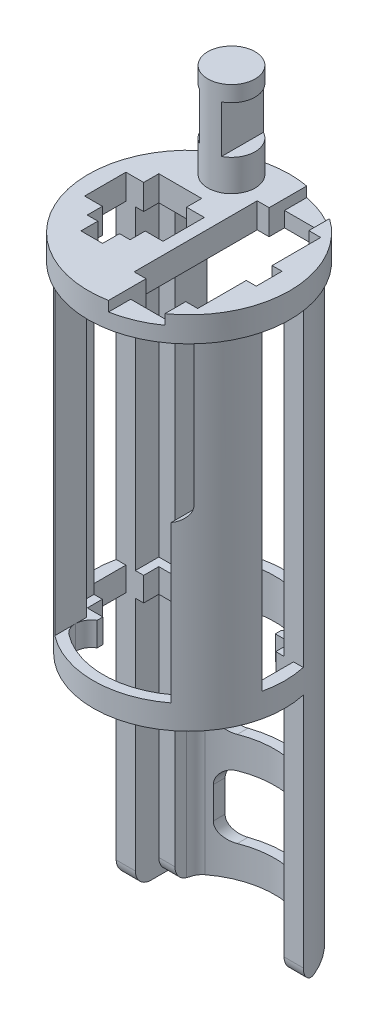
SolidWorks part; units mm, degrees
material "FormLabs Tough SLA- 3-D Printed"
ref_plane "Front Plane" through (0, 0, 0) normal (0, 0, 1) x (1, 0, 0)
ref_plane "Top Plane" through (0, 0, 0) normal (0, 1, 0) x (1, 0, 0)
ref_plane "Right Plane" through (0, 0, 0) normal (1, 0, 0) x (0, 0, -1)
sketch "Sketch2" plane through (0, 0, 0) normal (0, 1, 0) x (1, 0, 0)
  line L0 (23.0638, -3.692) -> (21.5138, -3.692) construction
  line L1 (23.0638, -2.492) -> (27.9638, -2.492) construction
  line L2 (23.0638, -2.492) -> (23.0638, -3.692) construction
  line L3 (23.0638, -8.892) -> (35.4638, -8.892) construction
  line L4 (35.4638, -2.492) -> (35.4638, -3.692) construction
  line L5 (21.5138, -3.692) -> (21.5138, -7.692) construction
  line L6 (21.5138, -7.692) -> (23.0638, -7.692) construction
  line L7 (35.4638, -3.692) -> (37.0138, -3.692) construction
  line L8 (37.0138, -3.692) -> (37.0138, -7.692) construction
  line L9 (37.0138, -7.692) -> (35.4638, -7.692) construction
  line L10 (27.9638, -2.492) -> (27.9638, -1.492) construction
  line L11 (27.9638, -1.492) -> (30.5638, -1.492) construction
  line L12 (30.5638, -1.492) -> (30.5638, -2.492) construction
  line L13 (21.5138, -5.692) -> (23.0638, -5.692) construction
  line L14 (23.0638, -5.692) -> (35.4638, -5.692) construction
  line L15 (35.4638, -5.692) -> (37.0138, -5.692) construction
  line L16 (23.0638, -7.692) -> (23.0638, -8.892) construction
  line L17 (35.4638, -7.692) -> (35.4638, -8.892) construction
  line L18 (23.0638, -3.692) -> (23.0638, -5.692) construction
  line L19 (23.0638, -5.692) -> (23.0638, -7.692) construction
  line L20 (35.4638, -7.692) -> (35.4638, -5.692) construction
  line L21 (35.4638, -5.692) -> (35.4638, -3.692) construction
  line L22 (29.2638, -5.692) -> (29.2638, -1.492) construction
  line L23 (30.5638, -2.492) -> (35.4638, -2.492) construction
  line L24 (6.6548, -2.0828) -> (8.4455, -2.0828)
  line L29 (6.6548, -3.6068) -> (1.0922, -3.6068) construction
  line L30 (6.6548, -3.6068) -> (6.6548, -2.0828)
  line L31 (6.6548, 3.6068) -> (-6.6548, 3.6068) construction
  line L32 (-6.6548, -3.6068) -> (-6.6548, -2.0828)
  line L33 (8.4455, -2.0828) -> (8.4455, 2.0828)
  line L34 (8.4455, 2.0828) -> (6.6548, 2.0828)
  line L35 (-6.6548, -2.0828) -> (-8.4455, -2.0828)
  line L36 (-8.4455, -2.0828) -> (-8.4455, 2.0828)
  line L37 (-8.4455, 2.0828) -> (-6.6548, 2.0828)
  line L38 (1.0922, -3.6068) -> (1.0922, -5.3086) construction
  line L39 (1.0922, -5.3086) -> (-1.0922, -5.3086) construction
  line L40 (-1.0922, -5.3086) -> (-1.0922, -3.6068) construction
  line L41 (8.4455, 0) -> (6.6548, 0) construction
  line L42 (6.6548, 0) -> (-6.6548, 0) construction
  line L43 (-6.6548, 0) -> (-8.4455, 0) construction
  line L44 (6.6548, 2.0828) -> (6.6548, 3.6068)
  line L45 (-6.6548, 2.0828) -> (-6.6548, 3.6068)
  line L46 (6.6548, -2.0828) -> (6.6548, 0) construction
  line L47 (6.6548, 0) -> (6.6548, 2.0828) construction
  line L48 (-6.6548, 2.0828) -> (-6.6548, 0) construction
  line L49 (-6.6548, 0) -> (-6.6548, -2.0828) construction
  line L50 (-6.6548, 3.6068) -> (-5.08, 3.6068)
  line L51 (-1.0922, -3.6068) -> (-6.6548, -3.6068) construction
  line L52 (-5.08, 3.6068) -> (-5.08, 4.191)
  line L53 (-8.1351, 5.1943) -> (8.1351, 5.1943) construction
  line L54 (-1.9685, -3.6068) -> (-1.9685, -6.6548) construction
  line L55 (-1.9685, -6.6548) -> (1.9685, -6.6548) construction
  line L56 (1.9685, -6.6548) -> (1.9685, -3.6068) construction
  line L57 (0, -6.6548) -> (0, -5.3086) construction
  line L58 (37.0138, -3.692) -> (37.7638, -3.692) construction
  line L59 (37.7638, -3.692) -> (37.7638, -7.692) construction
  line L60 (37.7638, -7.692) -> (37.0138, -7.692) construction
  line L61 (21.5138, -3.692) -> (20.7638, -3.692) construction
  line L62 (20.7638, -3.692) -> (20.7638, -7.692) construction
  line L63 (20.7638, -7.692) -> (21.5138, -7.692) construction
  line L64 (8.4455, 2.0828) -> (9.525, 2.0828) construction
  line L65 (9.525, 2.0828) -> (9.525, -2.0828) construction
  line L66 (9.525, -2.0828) -> (8.4455, -2.0828) construction
  line L67 (-8.4455, -2.0828) -> (-9.525, -2.0828) construction
  line L68 (-9.525, -2.0828) -> (-9.525, 2.0828) construction
  line L69 (-9.525, 2.0828) -> (-8.4455, 2.0828) construction
  line L73 (6.6548, 3.6068) -> (5.08, 3.6068)
  line L75 (0, 5.1943) -> (0, 9.652) construction
  line L76 (5.08, 3.6068) -> (5.08, 4.191)
  line L77 (6.6548, -3.6068) -> (5.08, -3.6068)
  line L78 (5.08, -3.6068) -> (5.08, -4.191)
  line L79 (-6.6548, -3.6068) -> (-5.08, -3.6068)
  line L80 (-5.08, -3.6068) -> (-5.08, -4.191)
  line L81 (-6.6548, 3.6068) -> (-6.6548, 4.191) construction
  line L82 (-6.6548, 4.191) -> (-5.08, 4.191) construction
  line L83 (6.6548, 3.6068) -> (6.6548, 4.191) construction
  line L84 (6.6548, 4.191) -> (5.08, 4.191) construction
  line L85 (-6.6548, -3.6068) -> (-6.6548, -4.191) construction
  line L86 (-6.6548, -4.191) -> (-5.08, -4.191) construction
  line L87 (6.6548, -3.6068) -> (6.6548, -4.191) construction
  line L88 (6.6548, -4.191) -> (5.08, -4.191) construction
  line L89 (5.08, -4.191) -> (5.8674, -4.191)
  line L90 (5.8674, -4.191) -> (5.8674, -6.3367)
  line L91 (-5.08, -4.191) -> (-5.8674, -4.191)
  line L92 (-5.8674, -4.191) -> (-5.8674, -6.3367)
  line L93 (-5.08, 4.191) -> (-5.8674, 4.191)
  line L94 (-5.8674, 4.191) -> (-5.8674, 6.3367)
  line L95 (5.08, 4.191) -> (5.8674, 4.191)
  line L96 (5.8674, 4.191) -> (5.8674, 6.3367)
  line L97 (6.6548, 4.191) -> (7.239, 4.191) construction
  line L98 (7.239, 4.191) -> (7.239, 2.0828) construction
  line L99 (6.6548, -4.191) -> (7.239, -4.191) construction
  line L100 (7.239, -4.191) -> (7.239, -2.0828) construction
  line L101 (-6.6548, -4.191) -> (-7.239, -4.191) construction
  line L102 (-7.239, -4.191) -> (-7.239, -2.0828) construction
  line L103 (-6.6548, 4.191) -> (-7.239, 4.191) construction
  line L104 (-7.239, 4.191) -> (-7.239, 2.0828) construction
  circle A1 centre (0, 0) radius 9.652
  arc A4 (-5.8674, -6.3367) -> (5.8674, -6.3367) centre (0, 0) ccw
  arc A5 (5.8674, 6.3367) -> (-5.8674, 6.3367) centre (0, 0) ccw
  point P85 (-5.8674, 4.191)
  point P86 (-5.08, 3.8989)
  dimension "D2" = 4
  dimension "D15" = 19.304
  dimension "D16" = 1.016
  dimension "D21" = 10.16
  dimension "D22" = 8.382
  dimension "D3" = 6.4
  dimension "D4" = 7.4
  dimension "D5" = 2.6
  dimension "D6" = 12.4
  dimension "D7" = 15.5
  dimension "D8" = 4.1656
  dimension "D9" = 7.2136
  dimension "D10" = 8.9154
  dimension "D11" = 2.1844
  dimension "D12" = 13.3096
  dimension "D13" = 16.891
  dimension "D14" = 1.5875
  dimension "D17" = 3.048
  dimension "D18" = 3.937
  dimension "D19" = 17
  dimension "D20" = 19.05
extrude "Boss-Extrude1" add sketch "Sketch2" along normal blind 2.413
sketch "Sketch3" plane through (0, 2.413, 0) normal (0, 1, 0) x (1, 0, 0)
  line L5 (6.6548, 0) -> (-6.6548, 0) construction
  line L6 (-5.8674, 7.6639) -> (-5.8674, 4.445)
  line L7 (-5.8674, 4.191) -> (-5.8674, 6.3367) construction
  line L8 (-5.8674, 4.445) -> (-7.493, 4.445)
  line L9 (-7.493, 4.445) -> (-7.493, 2.0828)
  line L10 (-8.4455, 2.0828) -> (-6.6548, 2.0828) construction
  line L11 (-7.493, 2.0828) -> (-9.4246, 2.0828)
  line L12 (-9.525, 2.0828) -> (-8.4455, 2.0828) construction
  line L13 (-5.8674, -7.6639) -> (-5.8674, -4.445)
  line L14 (-5.8674, -4.191) -> (-5.8674, -6.3367) construction
  line L15 (-5.8674, -4.445) -> (-7.493, -4.445)
  line L16 (-7.493, -4.445) -> (-7.493, -2.0828)
  line L17 (-6.6548, -2.0828) -> (-8.4455, -2.0828) construction
  line L18 (-7.493, -2.0828) -> (-9.4246, -2.0828)
  line L19 (-8.4455, -2.0828) -> (-9.525, -2.0828) construction
  line L20 (5.8674, -7.6639) -> (5.8674, -4.445)
  line L21 (5.8674, -4.191) -> (5.8674, -6.3367) construction
  line L22 (5.8674, -4.445) -> (7.493, -4.445)
  line L23 (7.493, -4.445) -> (7.493, -2.0828)
  line L24 (6.6548, -2.0828) -> (8.4455, -2.0828) construction
  line L25 (7.493, -2.0828) -> (9.4246, -2.0828)
  line L26 (9.525, -2.0828) -> (8.4455, -2.0828) construction
  line L27 (5.8674, 7.6639) -> (5.8674, 4.445)
  line L28 (5.8674, 4.191) -> (5.8674, 6.3367) construction
  line L29 (5.8674, 4.445) -> (7.493, 4.445)
  line L30 (7.493, 4.445) -> (7.493, 2.0828)
  line L31 (8.4455, 2.0828) -> (6.6548, 2.0828) construction
  line L32 (7.493, 2.0828) -> (9.4246, 2.0828)
  line L33 (8.4455, 2.0828) -> (9.525, 2.0828) construction
  line L34 (7.239, 4.191) -> (7.239, 2.0828) construction
  line L35 (6.6548, 4.191) -> (5.08, 4.191) construction
  arc A5 (5.8674, -7.6639) -> (9.4246, -2.0828) centre (0, 0) ccw
  circle A6 centre (0, 0) radius 9.652 construction
  arc A7 (-5.8674, 7.6639) -> (-9.4246, 2.0828) centre (0, 0) ccw
  arc A8 (-9.4246, -2.0828) -> (-5.8674, -7.6639) centre (0, 0) ccw
  arc A9 (9.4246, 2.0828) -> (5.8674, 7.6639) centre (0, 0) ccw
  dimension "D1" = 0.254
  dimension "D2" = 0.254
extrude "Boss-Extrude2" add sketch "Sketch3" along normal blind 31.75
sketch "Sketch4" plane through (0, 34.163, 0) normal (0, 1, 0) x (1, 0, 0)
  line L0 (0.6674, -6.2) -> (0.6674, 6.2)
  line L1 (0.6674, 6.2) -> (1.8674, 6.2)
  line L2 (7.0674, 6.2) -> (7.0674, 1.3)
  line L3 (7.0674, 1.3) -> (8.0674, 1.3)
  line L4 (8.0674, 1.3) -> (8.0674, -1.3)
  line L5 (8.0674, -1.3) -> (7.0674, -1.3)
  line L6 (7.0674, -1.3) -> (7.0674, -6.2)
  line L7 (7.0674, -6.2) -> (5.8674, -6.2)
  line L8 (5.8674, -6.2) -> (5.8674, -7.75)
  line L9 (5.8674, -7.75) -> (1.8674, -7.75)
  line L10 (1.8674, -7.75) -> (1.8674, -6.2)
  line L11 (1.8674, -6.2) -> (0.6674, -6.2)
  line L12 (1.8674, 6.2) -> (1.8674, 7.75)
  line L13 (1.8674, 7.75) -> (5.8674, 7.75)
  line L14 (5.8674, 7.75) -> (5.8674, 6.2)
  line L15 (5.8674, 6.2) -> (7.0674, 6.2)
  line L16 (5.8674, -4.191) -> (5.8674, -6.3367) construction
  line L17 (35.4638, -3.692) -> (37.0138, -3.692) construction
  line L18 (23.0638, -2.492) -> (23.0638, -3.692) construction
  line L19 (30.5638, -1.492) -> (30.5638, -2.492) construction
  line L20 (21.5138, -3.692) -> (21.5138, -7.692) construction
  line L21 (5.8674, -7.75) -> (5.8674, -8.5) construction
  line L22 (23.0638, -8.892) -> (35.4638, -8.892) construction
  line L23 (30.5638, -2.492) -> (35.4638, -2.492) construction
  line L24 (-8.4455, 2.0828) -> (-6.6548, 2.0828) construction
  line L25 (5.8674, -8.5) -> (1.8674, -8.5) construction
  line L26 (1.8674, -8.5) -> (1.8674, -7.75) construction
  line L27 (5.8674, 7.75) -> (5.8674, 8.5) construction
  line L28 (5.8674, 8.5) -> (1.8674, 8.5) construction
  line L29 (1.8674, 8.5) -> (1.8674, 7.75) construction
  line L30 (-6.6548, -2.0828) -> (-8.4455, -2.0828) construction
  line L31 (21.5138, -3.692) -> (20.7638, -3.692) construction
  line L32 (-8.4455, 2.0828) -> (-6.6548, 2.0828)
  line L33 (-6.6548, 2.0828) -> (-6.6548, 3.6068)
  line L34 (-6.6548, 3.6068) -> (-2.3368, 3.6068)
  line L36 (-2.3368, 3.6068) -> (-2.3368, 2.0828)
  line L37 (-2.3368, 2.0828) -> (-0.5461, 2.0828)
  line L39 (-2.3368, -3.6068) -> (-3.4036, -3.6068)
  line L40 (-3.4036, -3.6068) -> (-3.4036, -5.3086)
  line L41 (-3.4036, -5.3086) -> (-5.588, -5.3086)
  line L42 (-5.588, -5.3086) -> (-5.588, -3.6068)
  line L43 (-5.588, -3.6068) -> (-6.6548, -3.6068)
  line L44 (1.0922, -3.6068) -> (1.0922, -5.3086) construction
  line L45 (1.0922, -5.3086) -> (-1.0922, -5.3086) construction
  line L46 (-6.6548, -3.6068) -> (-6.6548, -2.0828)
  line L47 (-6.6548, -2.0828) -> (-8.4455, -2.0828)
  line L48 (-8.4455, -2.0828) -> (-8.4455, 2.0828)
  line L49 (-2.3368, -3.6068) -> (-2.3368, -2.0828)
  line L50 (-2.3368, -2.0828) -> (-0.5461, -2.0828)
  line L51 (-0.5461, -2.0828) -> (-0.5461, 2.0828)
  line L52 (-4.4958, 3.6068) -> (-4.4958, -5.3086) construction
  line L53 (-0.5461, 2.0828) -> (0.5334, 2.0828) construction
  line L54 (0.5334, 2.0828) -> (0.5334, -2.0828) construction
  line L55 (0.5334, -2.0828) -> (-0.5461, -2.0828) construction
  line L56 (-8.4455, -2.0828) -> (-9.525, -2.0828) construction
  line L58 (8.4455, 0) -> (6.6548, 0) construction
  circle A0 centre (0, 0) radius 10.16
  point P78 (8.0674, 0)
  dimension "D3" = 20.32
  dimension "D1" = 4.318
  dimension "D2" = 7.8994
extrude "Boss-Extrude3" add sketch "Sketch4" along normal blind 2.54
sketch "Sketch5" plane through (0, 34.163, 0) normal (0, 1, 0) x (1, 0, 0)
  line L9 (20.7638, -7.692) -> (23.0638, -7.692) construction
  line L11 (7.493, -4.445) -> (5.8674, -4.445) construction
  line L12 (5.8674, 4.445) -> (7.0674, 4.445)
  line L13 (5.8674, 4.445) -> (5.8674, 7.6639)
  line L15 (7.0674, 4.445) -> (7.0674, 6.5737)
  line L17 (7.0674, -6.5737) -> (7.0674, -4.445)
  line L18 (7.0674, -4.445) -> (5.8674, -4.445)
  line L19 (5.8674, -7.6639) -> (5.8674, -4.445)
  line L20 (7.0674, -4.445) -> (5.8674, -4.445) construction
  line L21 (7.0674, -6.2) -> (7.0674, -1.3) construction
  line L22 (6.6548, 0) -> (-6.6548, 0) construction
  arc A3 (5.8674, -7.6639) -> (7.0674, -6.5737) centre (0, 0) ccw
  circle A4 centre (0, 0) radius 9.652 construction
  arc A5 (7.0674, 6.5737) -> (5.8674, 7.6639) centre (0, 0) ccw
  point P1 (0, 0)
  point P2 (0, 0)
  point P7 (5.8676, 7.6637)
  point P18 (5.8674, 7.6967)
  point P22 (5.8674, 7.6409)
  point P23 (5.8677, 7.6636)
  point P25 (5.8674, -7.4989)
  point P33 (5.8674, -7.6581)
extrude "Cut-Extrude1" cut sketch "Sketch5" against normal blind 16.002
sketch "Sketch6" plane through (0, 36.703, 0) normal (0, 1, 0) x (1, 0, 0)
  line L0 (6.6548, 3.6068) -> (-6.6548, 3.6068) construction
  line L1 (0.6674, 6.2) -> (0.6674, -6.2) construction
  circle A0 centre (-2.9312, 7.2054) radius 2.3812
  circle A1 centre (0, 0) radius 10.16 construction
  circle A2 centre (-2.9312, 7.2054) radius 3.5986 construction
  dimension "D1" = 4.7625
extrude "Boss-Extrude4" add sketch "Sketch6" along normal blind 9.525
sketch "Sketch7" plane through (0, 0, 0) normal (0, 0, 1) x (1, 0, 0)
  line L0 (-0.5499, 36.703) -> (-0.5499, 46.228) construction
  line L1 (-5.3124, 44.6405) -> (-4.0424, 44.6405)
  line L2 (-5.3124, 44.6405) -> (-5.3124, 39.878)
  line L3 (-5.3124, 39.878) -> (-4.0424, 39.878)
  line L4 (-4.0424, 44.6405) -> (-4.0424, 39.878)
  line L5 (-0.5499, 44.6405) -> (-1.8199, 44.6405)
  line L6 (-0.5499, 44.6405) -> (-0.5499, 39.878)
  line L7 (-0.5499, 39.878) -> (-1.8199, 39.878)
  line L8 (-1.8199, 44.6405) -> (-1.8199, 39.878)
  line L9 (-0.5499, 46.228) -> (-5.3124, 46.228) construction
  line L10 (10.16, 36.703) -> (-10.16, 36.703) construction
  line L11 (-5.3124, 46.228) -> (-5.3124, 36.703) construction
  dimension "D1" = 1.5875
  dimension "D2" = 1.27
  dimension "D3" = 3.175
extrude "Cut-Extrude2" cut sketch "Sketch7" against normal blind 9.525
sketch "Sketch9" plane through (0, 0, 0) normal (0, -1, 0) x (1, 0, 0)
  line L0 (6.6548, 0) -> (-6.6548, 0) construction
  line L9 (-5.8674, -6.3367) -> (-5.8674, -4.445)
  line L10 (-5.8674, -4.445) -> (-7.493, -4.445)
  line L11 (-7.493, -4.445) -> (-7.493, -2.0828)
  line L12 (-7.493, -2.0828) -> (-9.4246, -2.0828)
  line L13 (5.8674, -6.3367) -> (5.8674, -4.445)
  line L14 (5.8674, -4.445) -> (7.493, -4.445)
  line L15 (7.493, -4.445) -> (7.493, -2.0828)
  line L16 (7.493, -2.0828) -> (9.4246, -2.0828)
  arc A2 (-9.4246, -2.0828) -> (9.4246, -2.0828) centre (0, 0) ccw
  circle A4 centre (0, 0) radius 9.652 construction
  arc A7 (-5.8674, -6.3367) -> (5.8674, -6.3367) centre (0, 0) ccw
  arc A8 (-5.8674, -6.3367) -> (5.8674, -6.3367) centre (0, 0) ccw construction
extrude "Boss-Extrude5" add sketch "Sketch9" along normal blind 25.4
sketch "Sketch10" plane through (0, 0, 0) normal (0, 0, -1) x (-1, 0, 0)
  line L0 (-5.8674, 0) -> (5.8674, 0) construction
  line L1 (-4.7625, -15.875) -> (4.7625, -15.875)
  line L2 (-4.7625, -15.875) -> (-4.7625, -22.225)
  line L3 (-4.7625, -22.225) -> (4.7625, -22.225)
  line L4 (4.7625, -15.875) -> (4.7625, -22.225)
  line L5 (-9.4246, -25.4) -> (9.4246, -25.4) construction
  line L6 (0, 0) -> (0, -1.5875) construction
  line L11 (-4.7625, -1.5875) -> (4.7625, -1.5875)
  line L12 (-4.7625, -1.5875) -> (-4.7625, -12.7)
  line L13 (-4.7625, -12.7) -> (4.7625, -12.7)
  line L14 (4.7625, -1.5875) -> (4.7625, -12.7)
  dimension "D1" = 1.5875
  dimension "D2" = 3.175
  dimension "D3" = 9.525
  dimension "D4" = 6.35
  dimension "D5" = 3.175
extrude "Cut-Extrude3" cut sketch "Sketch10" along normal blind 12.7
fillet "Fillet4" radius 1.5875 8 edges at (-4.7625, -22.225, -7.7997) (4.7625, -22.225, -7.7997) (4.7625, -15.875, -7.7997) (-4.7625, -15.875, -7.7997) (-4.7625, -1.5875, -7.7997) (4.7625, -1.5875, -7.7997) (4.7625, -12.7, -7.7997) (-4.7625, -12.7, -7.7997)
fillet "Fillet5" radius 1.5875 5 edges at (5.8674, -11.4935, -6.3367) (-5.8674, -11.4935, -6.3367) (5.8674, 1.2065, 6.3367) (-5.8674, 1.2065, 6.3367) (-5.8674, 1.2065, 4.191) tangent propagation no
fillet "Fillet6" radius 1.5875 2 edges at (7.0674, 18.161, -5.5093) (7.0674, 18.161, 5.5093)
fillet "Fillet7" radius 1.5875 4 edges at (-6.6802, -25.4, -4.445) (6.6802, -25.4, -4.445) (8.4588, -25.4, -2.0828) (-8.4588, -25.4, -2.0828)
sketch "Sketch11" plane through (0, 36.703, 0) normal (0, 1, 0) x (1, 0, 0)
  line L0 (1.8674, 7.75) -> (1.8674, 9.9869)
  line L1 (5.8674, 7.75) -> (5.8674, 8.2945)
  line L2 (5.8674, -7.75) -> (5.8674, -8.2945)
  line L3 (1.8674, -7.75) -> (1.8674, -9.9869)
  line L4 (1.8674, 7.75) -> (5.8674, 7.75)
  line L5 (1.8674, -7.75) -> (5.8674, -7.75)
  arc A0 (1.8674, -9.9869) -> (5.8674, -8.2945) centre (0, 0) ccw
  circle A1 centre (0, 0) radius 10.16 construction
  arc A2 (5.8674, 8.2945) -> (1.8674, 9.9869) centre (0, 0) ccw
extrude "Cut-Extrude4" cut sketch "Sketch11" against normal offset from surface (1.016 mm away) 1.524 up to face at (-5.585, 34.163, 0.6858)
sketch "Sketch12" plane through (0, 0, 0) normal (0, -1, 0) x (1, 0, 0)
  line L0 (5.8674, 4.191) -> (5.8674, 5.6003)
  line L1 (5.8674, 5.6003) -> (5.8674, 4.191) construction
  line L2 (5.8674, 4.191) -> (5.08, 4.191)
  line L3 (5.8674, -4.191) -> (5.8674, -5.6003)
  line L4 (5.8674, -4.445) -> (5.8674, -5.6003) construction
  line L5 (5.8674, -4.191) -> (5.08, -4.191)
  line L6 (-5.8674, -4.191) -> (-5.8674, -5.6003)
  line L7 (-5.8674, -4.445) -> (-5.8674, -7.6639) construction
  line L8 (-5.8674, -4.191) -> (-5.08, -4.191)
  arc A0 (5.08, -4.191) -> (5.8674, -5.6003) centre (4.2124, -5.6003) cw
  arc A1 (-5.8674, -5.6003) -> (-5.08, -4.191) centre (-4.2124, -5.6003) cw
  arc A2 (5.8674, 5.6003) -> (5.08, 4.191) centre (4.2124, 5.6003) cw
extrude "Boss-Extrude6" add sketch "Sketch12" against normal up to surface (2.413 mm away) up to face at (0, 2.413, -7.36)
